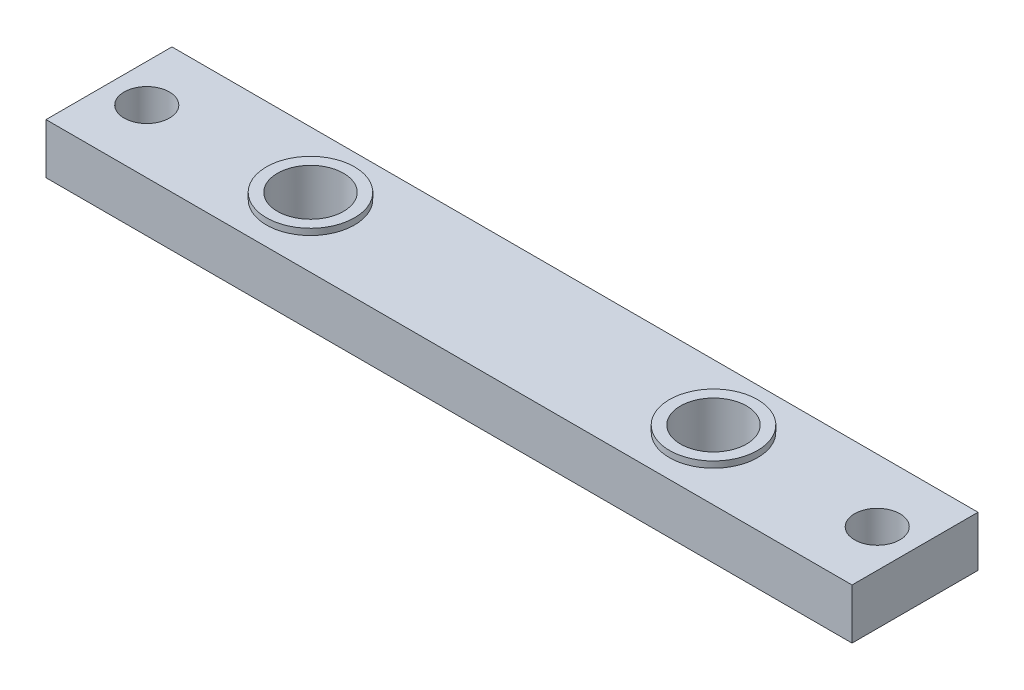
SolidWorks part; units mm, degrees
ref_plane "Front Plane" through (0, 0, 0) normal (0, 0, 1) x (1, 0, 0)
ref_plane "Top Plane" through (0, 0, 0) normal (0, 1, 0) x (1, 0, 0)
ref_plane "Right Plane" through (0, 0, 0) normal (1, 0, 0) x (0, 0, -1)
sketch "Sketch1" plane through (0, 0, 0) normal (0, 1, 0) x (1, 0, 0)
  line L0 (0, 5) -> (64, 5) construction
  line L1 (0, 0) -> (64, 0)
  line L2 (0, 0) -> (0, 10)
  line L3 (0, 10) -> (64, 10)
  line L4 (64, 0) -> (64, 10)
  line L5 (32, 10) -> (32, 0) construction
  circle A0 centre (3, 5) radius 1.8
  circle A2 centre (16, 5) radius 2.625
  circle A4 centre (16, 5) radius 3.5
  circle A6 centre (61, 5) radius 1.8
  circle A7 centre (48, 5) radius 3.5
  circle A8 centre (48, 5) radius 2.625
  dimension "D3" = 3.6
  dimension "D4" = 5.25
  dimension "D5" = 7
  dimension "D6" = 3
  dimension "D1" = 64
  dimension "D2" = 10
  dimension "D7" = 16
extrude "Boss-Extrude1" add sketch "Sketch1" along normal blind 4 contours L3 L4 L1 L2 | A0 | A2 | A6 | A8
extrude "Boss-Extrude2" add sketch "Sketch1<4>" along normal blind 0.5 from surface contours A4 | A2 | A8 | A7 starting at face at (48, 4, -7.625)
sketch "Sketch1<4>" plane through (0, 0, 0) normal (0, 1, 0) x (1, 0, 0) same geometry as "Sketch1"
